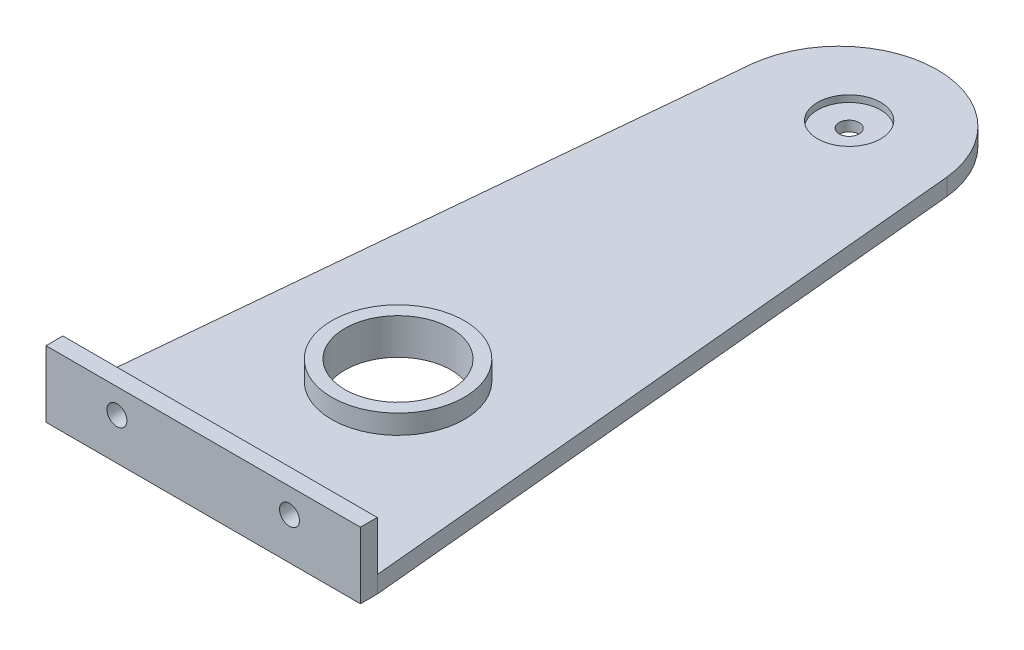
SolidWorks part; units mm, degrees
note: The reader was unsure of these and kept them because the rebuilt part matched: shared geometry of "Sketch2<6>", "Sketch2<8>".
ref_plane "Front Plane" through (0, 0, 0) normal (0, 0, 1) x (1, 0, 0)
ref_plane "Top Plane" through (0, 0, 0) normal (0, 1, 0) x (1, 0, 0)
ref_plane "Right Plane" through (0, 0, 0) normal (1, 0, 0) x (0, 0, -1)
sketch "Sketch2" plane through (0, 0, 0) normal (0, -1, 0) x (1, 0, 0)
  line L0 (-0.0202, 0) -> (0, 57.1196) construction
  line L1 (-0.0002, 68) -> (-0.0202, 0) construction
  line L5 (-0.0202, 46.4243) -> (-0.0202, 0) construction
  line L6 (14.7185, 0) -> (23.6804, 94.809)
  line L8 (-0.0202, 46.4243) -> (-0.0202, 94.809) construction
  line L9 (23.6804, 94.809) -> (-0.0202, 94.809) construction
  line L11 (9.8858, 9.7213) -> (-9.9262, 9.7213) construction
  line L12 (-14.7589, 0) -> (14.7185, 0) construction
  line L13 (-14.7589, 0) -> (-23.7006, 94.809)
  line L14 (23.6804, 94.809) -> (-23.7006, 94.809) construction
  line L15 (23.6804, 94.809) -> (-23.7006, 94.809)
  line L16 (23.6804, 94.809) -> (23.6804, 96.809)
  line L17 (23.6804, 96.809) -> (-23.7006, 96.809)
  line L18 (-23.7006, 96.809) -> (-23.7006, 94.809)
  circle A0 centre (-0.0202, 0) radius 4.7625
  circle A1 centre (-0.0202, 0) radius 1.5
  circle A2 centre (-0.0002, 68) radius 6.5
  arc A3 (14.7185, 0) -> (-14.7589, 0) centre (-0.0202, 1.5364) cw
  circle A4 centre (-0.0002, 68) radius 8
  circle A5 centre (-0.0202, 0) radius 47.3983 construction
  circle A6 centre (-0.0202, 0) radius 51.3983 construction
  circle A7 centre (-0.0002, 68) radius 10
  point P28 (-0.0202, 0)
extrude "Boss-Extrude3" add sketch "Sketch2" along normal blind 2.54
sketch "Sketch3" plane through (0, 0, 94.809) normal (0, 0, 1) x (1, 0, 0)
  line L0 (-23.7006, -2.54) -> (-23.7006, 7.46)
  line L1 (23.6804, -2.54) -> (23.6804, 7.46)
  line L2 (23.6804, 7.46) -> (-23.7006, 7.46)
  line L3 (23.6804, -2.54) -> (-23.7006, -2.54)
  line L4 (-13.0101, 3.73) -> (12.9899, 3.73) construction
  line L5 (-0.0101, 3.73) -> (-0.0101, -2.54) construction
  circle A4 centre (-13.0101, 3.73) radius 1.5
  circle A5 centre (12.9899, 3.73) radius 1.5
extrude "Boss-Extrude6" add sketch "Sketch3" along normal blind 2.54
extrude "Cut-Extrude2" cut sketch "Sketch2<6>" along normal blind 1 contours A0 A1 | A4 A2
sketch "Sketch2<6>" plane through (0, 0, 0) normal (0, -1, 0) x (1, 0, 0) same geometry as "Sketch2"
extrude "Boss-Extrude7" add sketch "Sketch2<8>" against normal blind 2.9 contours A7 A4
sketch "Sketch2<8>" plane through (0, 0, 0) normal (0, -1, 0) x (1, 0, 0) same geometry as "Sketch2"
